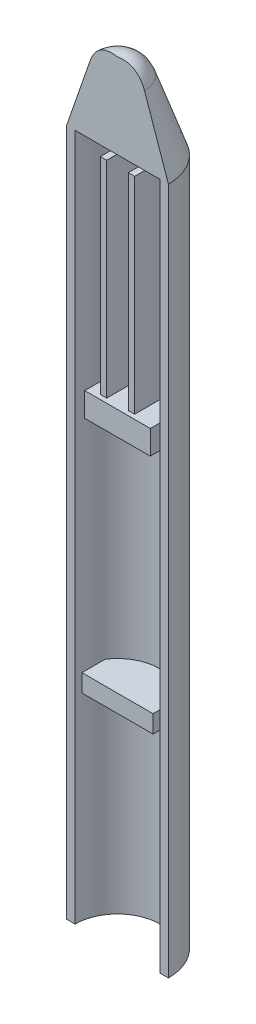
SolidWorks part; units mm, degrees
ref_plane "Front Plane" through (0, 0, 0) normal (0, 0, 1) x (1, 0, 0)
ref_plane "Top Plane" through (0, 0, 0) normal (0, 1, 0) x (1, 0, 0)
ref_plane "Right Plane" through (0, 0, 0) normal (1, 0, 0) x (0, 0, -1)
sketch "Sketch1" plane through (0, 0, 0) normal (0, 0, 1) x (1, 0, 0)
  line L0 (0, 91) -> (0, -91) construction
  line L1 (6.354, 87.279) -> (12, 71)
  line L2 (12, 71) -> (0, 71)
  line L3 (0, 91) -> (0, 71)
  spline S0 degree 2 poles (0, 91) (4.6686, 91.7236) (6.354, 87.279) knots 0 0 0 1 1 1
  point P3 (0, 0)
  point P4 (6.354, 87.279)
  dimension "D1" = 182
  dimension "D2" = 12
  dimension "D3" = 91
  dimension "D4" = 20
revolve "Revolve1" add sketch "Sketch1" angle 360 about L0
sketch "Sketch2" plane through (0, 0, 0) normal (0, 0, 1) x (1, 0, 0)
  line L0 (12, 71) -> (12, -91.0399)
  line L1 (12, -91.0399) -> (10, -91.0399)
  line L2 (10, -91.0399) -> (10, 71)
  line L3 (12, 71) -> (0, 71) construction
  line L4 (10, 71) -> (12, 71)
  dimension "D1" = 2
revolve "Revolve2" add sketch "Sketch2" angle 360 about L0
sketch "Sketch4" plane through (0, 0, 0) normal (0, 0, 1) x (1, 0, 0)
  line L0 (0, 91) -> (0, -91) construction
  line L5 (9, 10.6147) -> (-9, 10.6147)
  line L6 (9, 10.6147) -> (9, -34.3853)
  line L7 (9, -34.3853) -> (-9, -34.3853)
  line L8 (-9, 10.6147) -> (-9, -34.3853)
  line L9 (9, 10.6147) -> (-9, -34.3853) construction
  line L10 (9, -34.3853) -> (-9, 10.6147) construction
  line L11 (0, -100.299) -> (0, 100.299) construction
  line L12 (-7.7289, 13.3474) -> (7.7289, 13.3474)
  line L13 (-7.7289, 13.3474) -> (-7.7289, 19)
  line L14 (-7.7289, 19) -> (7.7289, 19)
  line L15 (7.7289, 13.3474) -> (7.7289, 19)
  line L16 (-7.7289, 13.3474) -> (7.7289, 19) construction
  line L17 (-7.7289, 19) -> (7.7289, 13.3474) construction
  line L18 (-8.3816, -43.0528) -> (8.3816, -43.0528)
  line L19 (-8.3816, -43.0528) -> (-8.3816, -38.896)
  line L20 (-8.3816, -38.896) -> (8.3816, -38.896)
  line L21 (8.3816, -43.0528) -> (8.3816, -38.896)
  line L22 (-8.3816, -43.0528) -> (8.3816, -38.896) construction
  line L23 (-8.3816, -38.896) -> (8.3816, -43.0528) construction
  line L24 (4.04, 20.0676) -> (2.54, 20.0676)
  line L25 (4.04, 20.0676) -> (4.04, 68.622)
  line L26 (4.04, 68.622) -> (2.54, 68.622)
  line L27 (2.54, 20.0676) -> (2.54, 68.622)
  line L28 (4.04, 20.0676) -> (2.54, 68.622) construction
  line L29 (4.04, 68.622) -> (2.54, 20.0676) construction
  line L30 (-4.04, 68.622) -> (-2.54, 20.0676) construction
  line L31 (-4.04, 20.0676) -> (-2.54, 68.622) construction
  line L32 (-2.54, 20.0676) -> (-2.54, 68.622)
  line L33 (-4.04, 68.622) -> (-2.54, 68.622)
  line L34 (-4.04, 20.0676) -> (-4.04, 68.622)
  line L35 (-4.04, 20.0676) -> (-2.54, 20.0676)
  line L36 (-2.54, 68.622) -> (2.54, 68.622)
  line L37 (-2.54, 20.0676) -> (2.54, 20.0676)
  point P0 (0, -11.8853)
  point P1 (0, 16.1737)
  point P12 (0, -40.9744)
  point P17 (0, 19)
  point P19 (3.29, 44.3448)
  point P30 (-3.29, 44.3448)
  dimension "D1" = 45
  dimension "D2" = 18
  dimension "D3" = 52
  dimension "D4" = 1.5
  dimension "D5" = 2.54
extrude "Boss-Extrude1" add sketch "Sketch4" against normal up to next contours L12 L15 L14 L13 | L18 L21 L20 L19 | L27 L24 L25 L26 | L34 L35 L32 L33 region at (0, 16.1737, 0) region at (0, -40.9744, 0) region at (3.29, 44.3448, 0) region at (-3.29, 44.3448, 0)
extrude "Boss-Extrude2" add sketch "Sketch4<4>" against normal up to next from offset 9.5 contours L32 L37 L27 L36 region at (0, 44.3448, 0) offset against normal yes
sketch "Sketch4<4>" plane through (0, 0, 0) normal (0, 0, 1) x (1, 0, 0) same geometry as "Sketch4"
sketch "Sketch5" plane through (0, 0, 0) normal (0, 0, 1) x (1, 0, 0)
  line L1 (36.3918, -96.4232) -> (-36.3918, -96.4232)
  line L2 (36.3918, -96.4232) -> (36.3918, 96.4232)
  line L3 (36.3918, 96.4232) -> (-36.3918, 96.4232)
  line L4 (-36.3918, -96.4232) -> (-36.3918, 96.4232)
  line L5 (36.3918, -96.4232) -> (-36.3918, 96.4232) construction
  line L6 (36.3918, 96.4232) -> (-36.3918, -96.4232) construction
  point P0 (0, 0)
extrude "Cut-Extrude1" cut sketch "Sketch5" along normal through all
